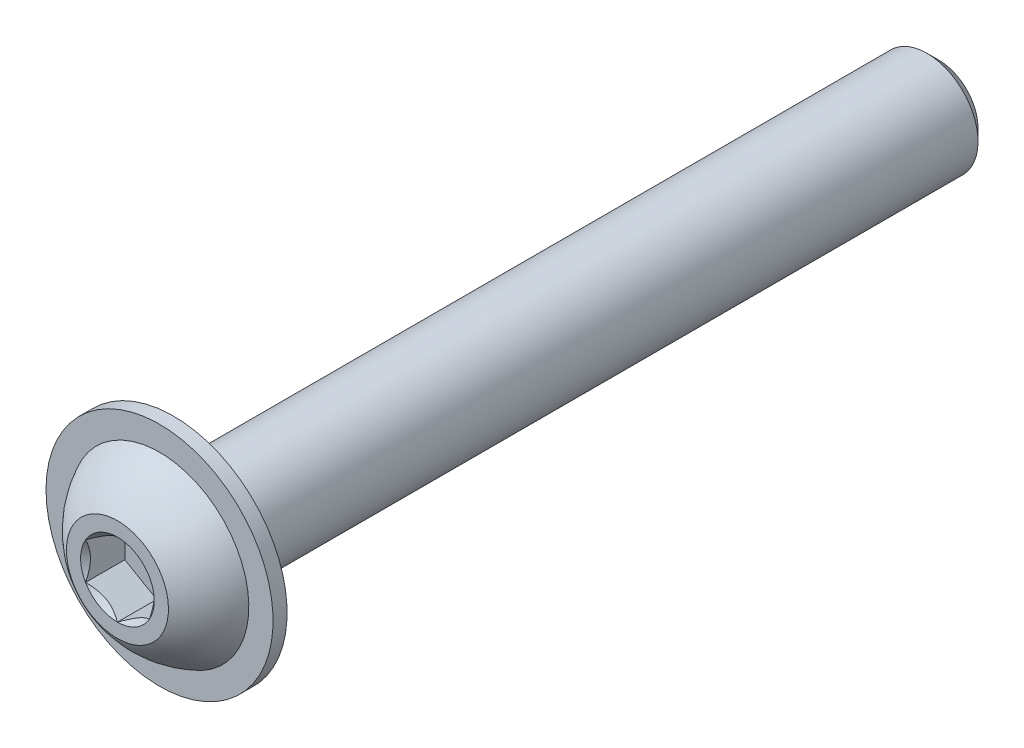
SolidWorks part; units mm, degrees
material "AISI 304"
ref_plane "Front" through (0, 0, 0) normal (0, 0, 1) x (1, 0, 0)
ref_plane "Top" through (0, 0, 0) normal (0, 1, 0) x (1, 0, 0)
ref_plane "Right" through (0, 0, 0) normal (1, 0, 0) x (0, 0, -1)
sketch "Sketch1" plane through (0, 0, 0) normal (1, 0, 0) x (0, 0, -1)
  line L2 (4.4, 4) -> (64.4, 4)
  line L3 (64.4, 4) -> (64.4, 0)
  line L4 (64.4, 0) -> (4.4, 0)
  line L6 (3.3, 7) -> (4.4, 7) construction
  line L7 (64.4, 4) -> (64.4, -4) construction
  line L8 (0, 0) -> (4.4, 0) construction
  line L9 (4.4, 7) -> (4.4, -7) construction
  line L11 (4.4, 4) -> (4.4, 0)
  line L13 (0, 2.5) -> (0, -2.5) construction
  line L14 (0, 2.5) -> (0, 4) construction
  line L15 (3.3, 7) -> (3.3, 8.9) construction
  line L16 (3.3, 8.9) -> (4.4, 8.9) construction
  line L17 (4.4, 8.9) -> (4.4, 7) construction
  line L18 (4.4, 8.9) -> (4.4, -8.9) construction
  arc A3 (0, 4) -> (3.3, 7) centre (6.65, 0) cw construction
  dimension "D1" = 1.1
revolve "Revolve1" add sketch "Sketch1" angle 360 mid plane about L4
sketch "Sketch10" plane through (0, 0, 0) normal (1, 0, 0) x (0, 0, -1)
  line L0 (64.4, 4) -> (64.4, -4) construction
  point P0 (62.525, -4)
  dimension "D1" = 1.875
sketch "Sketch3" plane through (0, 0, -64.4) normal (0, 0, -1) x (-1, 0, 0)
  circle A0 centre (0, 0) radius 4
sketch "Sketch2" plane through (0, 0, 0) normal (1, 0, 0) x (0, 0, -1)
  line L0 (64.4, 4) -> (65.4938, 4) construction
  line L1 (65.4938, 4) -> (65.025, 3.1881)
  line L2 (65.025, 3.1881) -> (64.8688, 3.1881)
  line L3 (64.8688, 3.1881) -> (64.4, 4)
  line L4 (64.6344, 3.5941) -> (65.2594, 3.5941) construction
  line L5 (64.2594, 4.2436) -> (65.6344, 4.2436)
  line L6 (64.9469, 3.1881) -> (64.9469, 4.2436) construction
  line L7 (65.4938, 4) -> (65.6344, 4.2436)
  line L8 (64.2594, 4.2436) -> (64.4, 4)
  point P7 (64.9469, 4.2436)
  point P8 (64.9469, 4)
  dimension "D1" = 60
  dimension "D2" = 0.1562
  dimension "D3" = 0.625
  dimension "D4" = 1.375
chamfer "Chamfer1" distance 0.9375 angle 45 1 edges at (0, 4, -64.4)
sketch "Sketch7" plane through (0, 0, 0) normal (1, 0, 0) x (0, 0, -1)
  line L6 (3.3, 7) -> (4.4, 7) construction
  line L8 (0, 0) -> (4.4, 0) construction
  line L11 (4.4, 7) -> (4.4, -7) construction
  line L12 (3.3, 7) -> (4.4, 7)
  line L13 (0, 0) -> (4.4, 0)
  line L14 (0, 2.5) -> (0, -2.5) construction
  line L15 (4.4, 7) -> (4.4, 0)
  line L16 (0, 4) -> (0, 0)
  arc A2 (3.3, 7) -> (0, 4) centre (6.65, 0) ccw construction
  arc A3 (3.3, 7) -> (0, 4) centre (6.65, 0) ccw
revolve "Revolve2" add sketch "Sketch7" angle 360 mid plane about L13
sketch "Sketch11" plane through (0, 0, -4.4) normal (0, 0, -1) x (-1, 0, 0)
  circle A0 centre (0, 0) radius 8.9
extrude "Boss-Extrude3" add sketch "Sketch11" against normal up to vertex (1.1 mm away) up to point (0, 7, -3.3)
sketch "Sketch5" plane through (0, 0, 0) normal (0, 0, 1) x (1, 0, 0)
  line L1 (2.5, -1.4434) -> (2.5, 1.4434)
  line L2 (2.5, 1.4434) -> (0, 2.8868)
  line L3 (0, 2.8868) -> (-2.5, 1.4434)
  line L4 (-2.5, 1.4434) -> (-2.5, -1.4434)
  line L5 (-2.5, -1.4434) -> (0, -2.8868)
  line L6 (0, -2.8868) -> (2.5, -1.4434)
  circle A0 centre (0, 0) radius 2.5 construction
extrude "Cut-Extrude2" cut sketch "Sketch5" against normal blind 3.08
sketch "Sketch6" plane through (0, 0, 0) normal (0, 0, 1) x (1, 0, 0)
  circle A0 centre (0, 0) radius 2.8868
extrude "Cut-Extrude3" cut sketch "Sketch6" against normal blind 3.08 draft 45
ref_plane "Plane2" through (0, 0, -4.4) normal (0, 0, -1) x (-1, 0, 0)
split "Split1" trim tools "Plane2" bodies to split 113 resulting bodies 120 121
curve "Helix/Spiral1" pitch 1.25 height 61.25 turns 49
sweep "Cut-Sweep1" [suppressed] cut profiles "Sketch2" path "Helix/Spiral1"
ref_axis "Center Axis 1" through (0, 0, -4.4) along (0, 0, -1)
ref_plane "Contact Plane 1" through (0, 0, -4.4) normal (0, 0, -1) x (-1, 0, 0)
equation "\"D3@Helix/Spiral1\" = \"Lg@Sketch1\" + \"D4@Helix/Spiral1\""
equation "\"D2@Sketch2\" = \"D4@Helix/Spiral1\" * .125"
equation "\"D3@Sketch2\" = \"D4@Helix/Spiral1\" * .5"
equation "\"D1@Chamfer1\" = \"D4@Helix/Spiral1\" * .75"
equation "\"D1@Cut-Extrude2\" = \"Head Ht@Sketch1\" * .7"
equation "\"D1@Sketch1\" = \"Head Ht@Sketch1\" * .25"
equation "\"D1@Sketch10\" = \"D4@Helix/Spiral1\" * 1.5"
equation "\"D1@Cut-Extrude3\" = \"D1@Cut-Extrude2\""
equation "\"D4@Sketch2\"=\"D3@Sketch2\"*2.2"
